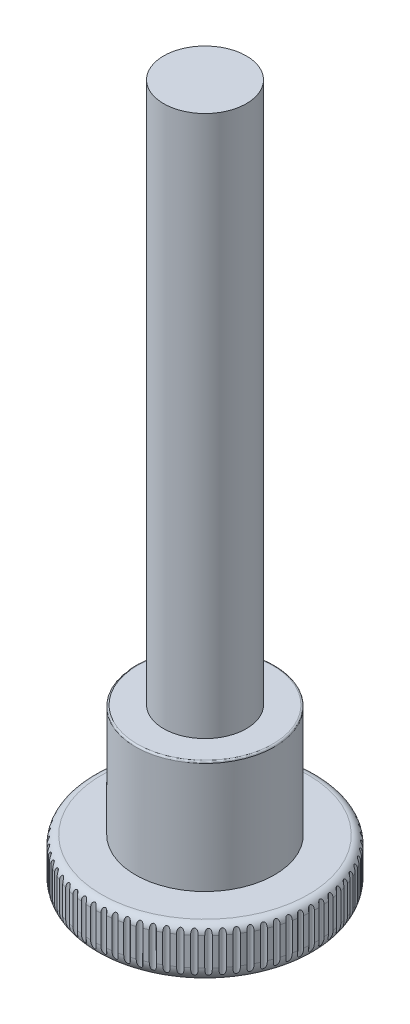
SolidWorks part; units mm, degrees
ref_plane "Alzado" through (0, 0, 0) normal (0, 0, 1) x (1, 0, 0)
ref_plane "Planta" through (0, 0, 0) normal (0, 1, 0) x (1, 0, 0)
ref_plane "Vista lateral" through (0, 0, 0) normal (1, 0, 0) x (0, 0, -1)
sketch "Croquis1" plane through (0, 0, 0) normal (0, 0, 1) x (1, 0, 0)
  line L0 (0, 0) -> (0, 74.5369) construction
  line L1 (0, 0) -> (6.75, 0)
  line L2 (6.75, 0) -> (6.75, 3.2)
  line L3 (6.75, 3.2) -> (4.2, 3.2)
  line L4 (4.2, 3.2) -> (4.2, 10)
  line L5 (4.2, 10) -> (2.5, 10)
  line L6 (2.5, 10) -> (2.5, 42.7)
  line L7 (2.5, 42.7) -> (0, 42.7)
  line L8 (0, 42.7) -> (0, 0)
  dimension "D1" = 3.2
  dimension "D2" = 10
  dimension "D3" = 42.7
  dimension "D4" = 13.5
  dimension "D5" = 8.4
  dimension "D6" = 5
revolve "Revolución1" add sketch "Croquis1" angle 360 about L0
fillet "Redondeo1" radius 1 1 edges at (0, 0, -6.75)
fillet "Redondeo3" radius 0.5 1 edges at (0, 3.2, -6.75)
sketch "Croquis3" plane through (0, 3.2, 0) normal (0, 1, 0) x (1, 0, 0)
  circle A0 centre (0, 6.8231) radius 0.1788
extrude "Cortar-Extruir2" cut sketch "Croquis3" against normal blind 30.2
pattern_circular "MatrizC1" count 70 over 360 about axis through (0, 2.7, 0) along (0, -1, 0) of "Cortar-Extruir2"
sketch "Croquis4" plane through (0, 0, 0) normal (0, -1, 0) x (1, 0, 0)
  line L1 (-2.5981, 0) -> (-1.299, -2.25)
  line L2 (-1.299, -2.25) -> (1.299, -2.25)
  line L3 (1.299, -2.25) -> (2.5981, 0)
  line L4 (2.5981, 0) -> (1.299, 2.25)
  line L5 (1.299, 2.25) -> (-1.299, 2.25)
  line L6 (-1.299, 2.25) -> (-2.5981, 0)
  circle A0 centre (0, 0) radius 2.25 construction
  dimension "D1" = 4.5
extrude "Cortar-Extruir3" cut sketch "Croquis4" against normal blind 4
sketch "Croquis5" plane through (0, 0, 0) normal (1, 0, 0) x (0, 0, -1)
  line L0 (0, 0) -> (0, 6.7345) construction
  spline S0 degree 3 poles (1.6237, -0.6999) (1.7252, 0.7702) (2.5794, 0.2497) (3.2334, -0.6566) (1.6237, -0.6999) (1.7252, 0.7702) (2.5794, 0.2497) knots -0.802598 -0.5638 -0.269332 0 0.197402 0.4362 0.730668 1 1.197402 1.4362 1.730668 only from (1.9022, 0.4943) to (1.9022, 0.4943)
revolve "Cortar-Revolución2" cut sketch "Croquis5" angle 360 about L0
sketch "Croquis6" plane through (0, 0, 0) normal (1, 0, 0) x (0, 0, -1)
  line L0 (0, 4) -> (0, 5.2496) construction
  line L1 (2.25, 4) -> (0, 4) construction
  line L2 (2.25, 4) -> (2.25, 0.1423) construction
  spline S0 degree 3 poles (1.0536, 5.7037) (1.5335, 3.9489) (2.0873, 3.929) (2.2042, 3.5315) (3.3357, 2.9869) (1.0536, 5.7037) (1.5335, 3.9489) (2.0873, 3.929) knots -0.814082 -0.694891 -0.209743 0 0.088251 0.185918 0.305109 0.790257 1 1.088251 1.185918 1.305109 only from (1.7241, 4) to (1.7241, 4)
revolve "Revolución3" add sketch "Croquis6" angle 360 about L0
fillet "Redondeo4" radius 0.1 1 edges at (0, 10, -4.2)
